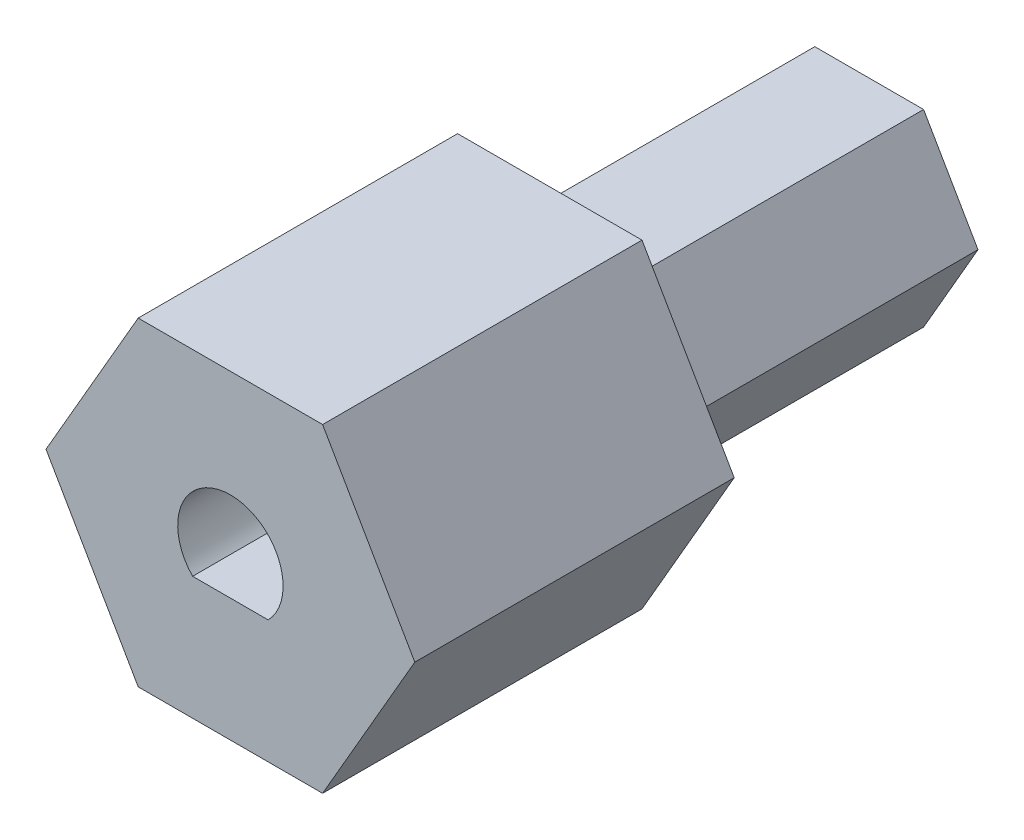
SolidWorks part; units mm, degrees
ref_plane "Front Plane" through (0, 0, 0) normal (0, 0, 1) x (1, 0, 0)
ref_plane "Top Plane" through (0, 0, 0) normal (0, 1, 0) x (1, 0, 0)
ref_plane "Right Plane" through (0, 0, 0) normal (1, 0, 0) x (0, 0, -1)
sketch "Sketch1" plane through (0, 0, 0) normal (0, 0, 1) x (1, 0, 0)
  line L1 (3.4064, 0) -> (1.7032, 2.95)
  line L2 (1.7032, 2.95) -> (-1.7032, 2.95)
  line L3 (-1.7032, 2.95) -> (-3.4064, 0)
  line L4 (-3.4064, 0) -> (-1.7032, -2.95)
  line L5 (-1.7032, -2.95) -> (1.7032, -2.95)
  line L6 (1.7032, -2.95) -> (3.4064, 0)
  circle A0 centre (0, 0) radius 2.95 construction
  dimension "D1" = 5.9
extrude "Boss-Extrude1" add sketch "Sketch1" along normal blind 20
sketch "Sketch2" plane through (0, 0, 20) normal (0, 0, 1) x (1, 0, 0)
  line L1 (-5.7735, 0) -> (-2.8868, -5)
  line L2 (-2.8868, -5) -> (2.8868, -5)
  line L3 (2.8868, -5) -> (5.7735, 0)
  line L4 (5.7735, 0) -> (2.8868, 5)
  line L5 (2.8868, 5) -> (-2.8868, 5)
  line L6 (-2.8868, 5) -> (-5.7735, 0)
  circle A0 centre (0, 0) radius 5 construction
  dimension "D1" = 10
extrude "Boss-Extrude2" add sketch "Sketch2" against normal blind 10 contours L1 L2 L3 L4 L5 L6
sketch "Sketch4" plane through (0, 0, 20) normal (0, 0, 1) x (1, 0, 0)
  line L0 (0, 0) -> (0, -1) construction
  line L1 (-1.1832, -1.15) -> (1.1832, -1.15)
  arc A0 (-1.1832, -1.15) -> (1.1832, -1.15) centre (0, 0) cw
  point P5 (0, 1.65)
  point P8 (0, -1)
  dimension "D1" = 1.65
  dimension "D2" = 1
  dimension "D3" = 2.8
extrude "Cut-Extrude1" cut sketch "Sketch4" against normal blind 11 contours L1 A0
